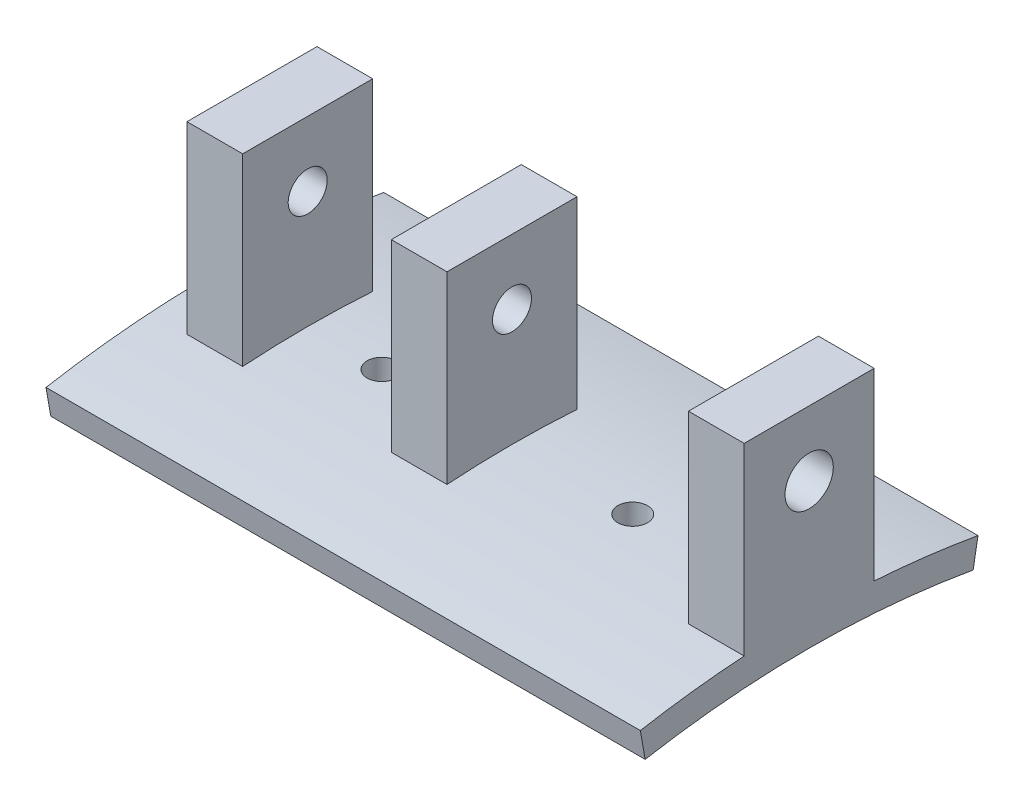
SolidWorks part; units mm, degrees
ref_plane "Front Plane" through (0, 0, 0) normal (0, 0, 1) x (1, 0, 0)
ref_plane "Top Plane" through (0, 0, 0) normal (0, 1, 0) x (1, 0, 0)
ref_plane "Right Plane" through (0, 0, 0) normal (1, 0, 0) x (0, 0, -1)
sketch "Base Sketch" plane through (0, 0, 0) normal (0, 0, 1) x (1, 0, 0)
  line L0 (-3000, 0) -> (3000, 0) construction
  line L1 (-630, 101.7) -> (-566, 101.7)
  line L2 (-566, 101.7) -> (-566, 104.7)
  line L3 (-566, 104.7) -> (-630, 104.7)
  line L4 (-630, 104.7) -> (-630, 101.7)
revolve "Base" add sketch "Base Sketch" angle 20 mid plane about L0
ref_axis "Engine Axis" through (-562.8, 0, 0) along (-1, 0, 0)
sketch "Upper Ear Sketch" plane through (0, 0, 0) normal (0, 0, 1) x (1, 0, 0)
  line L0 (-626, 103.5) -> (-620, 103.5)
  line L1 (-620, 103.5) -> (-620, 124.3)
  line L2 (-620, 124.3) -> (-626, 124.3)
  line L3 (-626, 124.3) -> (-626, 103.5)
extrude "Upper Ear" add sketch "Upper Ear Sketch" along normal mid plane 14
sketch "Lower Ear Sketch" plane through (0, 0, 0) normal (0, 0, 1) x (1, 0, 0)
  line L0 (-604, 103.5) -> (-598, 103.5)
  line L1 (-598, 103.5) -> (-598, 124.3)
  line L2 (-598, 124.3) -> (-604, 124.3)
  line L3 (-604, 124.3) -> (-604, 103.5)
extrude "Lower Ear" add sketch "Lower Ear Sketch" along normal mid plane 14
sketch "Stop Sketch" plane through (0, 0, 0) normal (0, 0, 1) x (1, 0, 0)
  line L0 (-572, 103.5) -> (-566, 103.5)
  line L1 (-566, 103.5) -> (-566, 124.3)
  line L2 (-566, 124.3) -> (-572, 124.3)
  line L3 (-572, 124.3) -> (-572, 103.5)
extrude "Stop" add sketch "Stop Sketch" along normal mid plane 14
ref_plane "Upper Ear Hole Plane" through (-626, 0, 0) normal (1, 0, 0) x (0, 0, -1)
sketch "Upper Ear Hole Sketch" plane through (-626, 0, 0) normal (1, 0, 0) x (0, 0, -1)
  circle A0 centre (0, 117.3) radius 2.1
extrude "Upper Ear Hole" cut sketch "Upper Ear Hole Sketch" along normal blind 6
ref_plane "Lower Ear Hole Plane" through (-604, 0, 0) normal (1, 0, 0) x (0, 0, -1)
sketch "Lower Ear Hole Sketch" plane through (-604, 0, 0) normal (1, 0, 0) x (0, 0, -1)
  circle A0 centre (0, 117.3) radius 2.1
extrude "Lower Ear Hole" cut sketch "Lower Ear Hole Sketch" along normal blind 6
ref_plane "Stop Hole Plane" through (-572, 0, 0) normal (1, 0, 0) x (0, 0, -1)
sketch "Stop Hole Sketch" plane through (-572, 0, 0) normal (1, 0, 0) x (0, 0, -1)
  circle A0 centre (0, 117.3) radius 2.6
extrude "Stop Hole" cut sketch "Stop Hole Sketch" along normal blind 6
ref_plane "Screw Hole 0 Plane" through (0, 0, 0) normal (0, 1, 0) x (-1, 0, 0)
sketch "Screw Hole 0 Sketch" plane through (0, 0, 0) normal (0, 1, 0) x (-1, 0, 0)
  circle A0 centre (585, 0) radius 1.6
extrude "Screw Hole 0" cut sketch "Screw Hole 0 Sketch" along normal blind 200
ref_plane "Screw Hole 1 Plane" through (0, 0, 0) normal (0, 1, 0) x (-1, 0, 0)
sketch "Screw Hole 1 Sketch" plane through (0, 0, 0) normal (0, 1, 0) x (-1, 0, 0)
  circle A0 centre (612, 0) radius 1.6
extrude "Screw Hole 1" cut sketch "Screw Hole 1 Sketch" along normal blind 200
